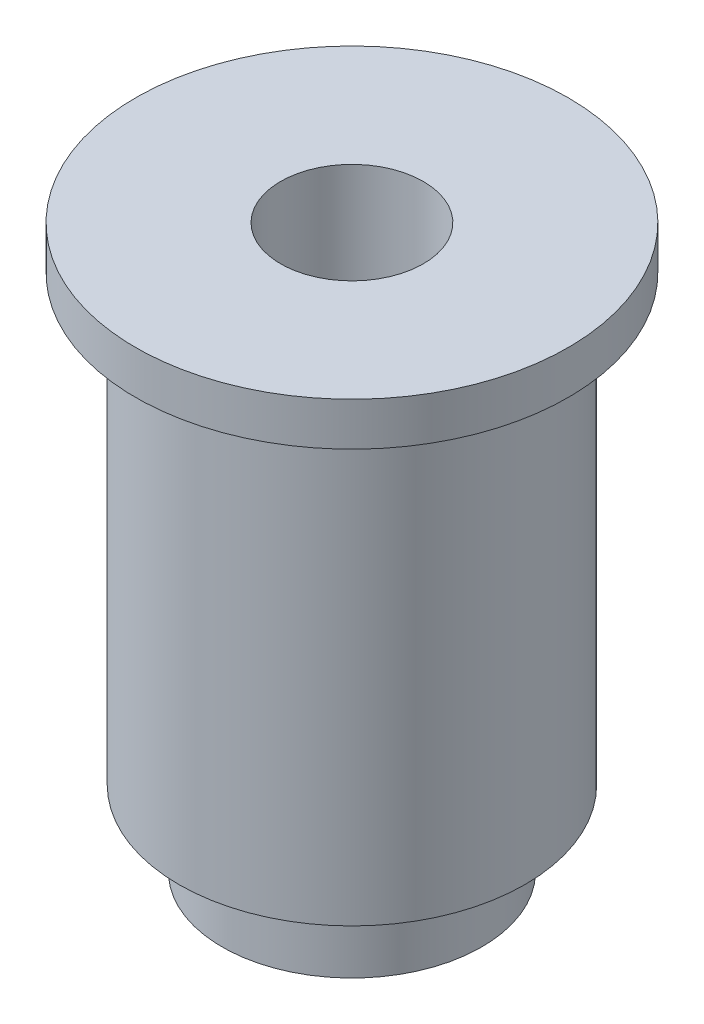
SolidWorks part; units mm, degrees
ref_plane "Front" through (0, 0, 0) normal (0, 0, 1) x (1, 0, 0)
ref_plane "Top" through (0, 0, 0) normal (0, 1, 0) x (1, 0, 0)
ref_plane "Right" through (0, 0, 0) normal (1, 0, 0) x (0, 0, -1)
sketch "Esquisse1" plane through (0, 0, 0) normal (0, 0, 1) x (1, 0, 0)
  line L0 (0, 0) -> (0, 25.3714) construction
  line L1 (1.65, 13) -> (5, 13)
  line L2 (5, 13) -> (5, 12)
  line L3 (5, 12) -> (4, 12)
  line L4 (4, 12) -> (4, 1.75)
  line L5 (4, 1.75) -> (3, 1.75)
  line L6 (3, 1.75) -> (3, 0)
  line L7 (3, 0) -> (1.65, 0)
  line L8 (1.65, 0) -> (1.65, 13)
  dimension "D1" = 10.25
  dimension "D2" = 10
  dimension "D3" = 8
  dimension "D4" = 6
  dimension "D5" = 13
  dimension "D6" = 1
  dimension "D7" = 3.3
revolve "Révolution1" add sketch "Esquisse1" angle 360 about L0
